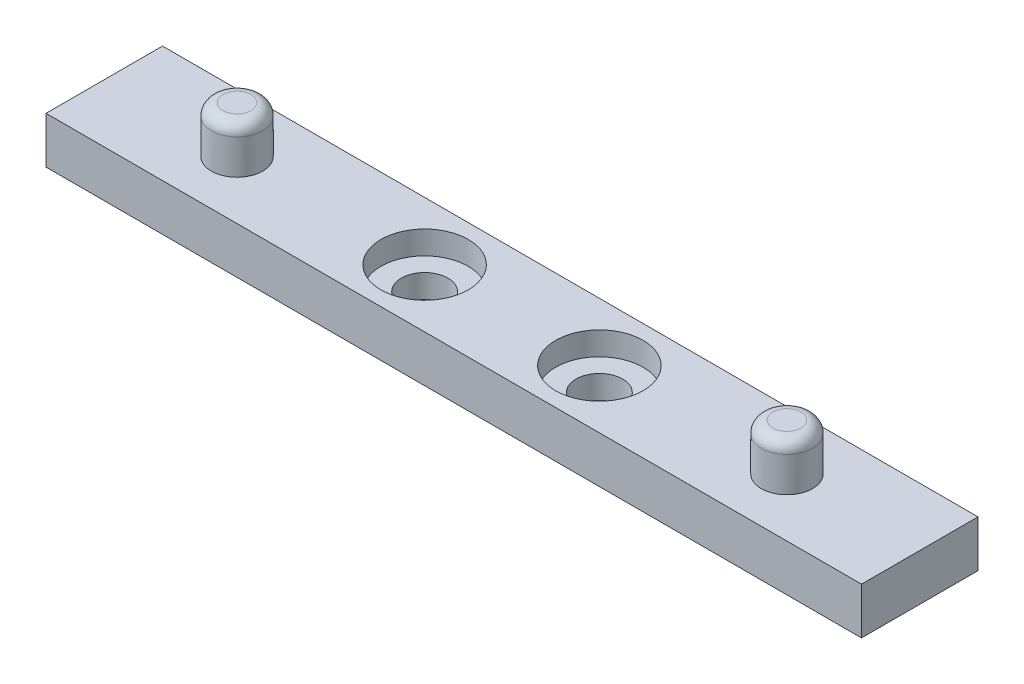
SolidWorks part; units mm, degrees
ref_plane "Front Plane" through (0, 0, 0) normal (0, 0, 1) x (1, 0, 0)
ref_plane "Top Plane" through (0, 0, 0) normal (0, 1, 0) x (1, 0, 0)
ref_plane "Right Plane" through (0, 0, 0) normal (1, 0, 0) x (0, 0, -1)
sketch "Sketch1" plane through (0, 0, 0) normal (0, 1, 0) x (1, 0, 0)
  line L0 (0, 6.35) -> (88.9, 6.35) construction
  line L1 (0, 0) -> (88.9, 0)
  line L2 (0, 0) -> (0, 12.7)
  line L3 (0, 12.7) -> (88.9, 12.7)
  line L4 (88.9, 0) -> (88.9, 12.7)
  line L5 (44.45, 12.7) -> (44.45, 0) construction
  circle A0 centre (34.925, 6.35) radius 2.54
  circle A1 centre (53.975, 6.35) radius 2.54
  dimension "D5" = 5.08
  dimension "D6" = 5.08
  dimension "D1" = 12.7
  dimension "D2" = 88.9
  dimension "D3" = 19.05
  dimension "D4" = 9.525
extrude "Boss-Extrude2" add sketch "Sketch1" along normal blind 5.08
sketch "Sketch2" plane through (0, 5.08, 0) normal (0, 1, 0) x (1, 0, 0)
  line L0 (0, 6.35) -> (88.9, 6.35) construction
  line L1 (0, 12.7) -> (0, 0) construction
  line L2 (88.9, 0) -> (88.9, 12.7) construction
  line L3 (44.45, 12.7) -> (44.45, 0) construction
  line L4 (88.9, 12.7) -> (0, 12.7) construction
  line L5 (0, 0) -> (88.9, 0) construction
  circle A0 centre (14.478, 6.35) radius 2.794
  circle A1 centre (74.422, 6.35) radius 2.794
  dimension "D1" = 5.588
  dimension "D2" = 5.588
  dimension "D3" = 59.944
  dimension "D4" = 29.972
extrude "Boss-Extrude3" add sketch "Sketch2" along normal blind 5.08
fillet "Fillet1" radius 1.27 2 edges at (74.422, 10.16, -3.556) (14.478, 10.16, -3.556)
sketch "Sketch3" plane through (0, 5.08, 0) normal (0, 1, 0) x (1, 0, 0)
  circle A0 centre (34.925, 6.35) radius 4.7625
  circle A1 centre (53.975, 6.35) radius 4.7625
  dimension "D1" = 9.525
  dimension "D2" = 9.525
extrude "Cut-Extrude1" cut sketch "Sketch3" against normal blind 2.54
